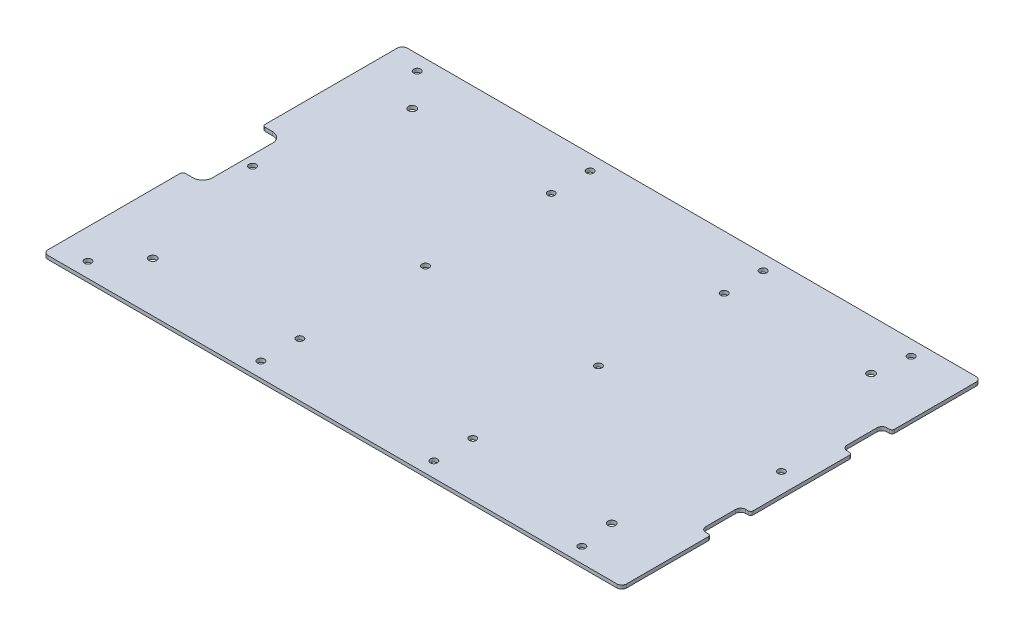
SolidWorks part; units mm, degrees
material "1060 Alloy"
ref_plane "Front" through (0, 0, 0) normal (0, 0, 1) x (1, 0, 0)
ref_plane "Top" through (0, 0, 0) normal (0, 1, 0) x (1, 0, 0)
ref_plane "Right" through (0, 0, 0) normal (1, 0, 0) x (0, 0, -1)
sketch "Sketch1" plane through (0, 0, 0) normal (0, 1, 0) x (1, 0, 0)
  line L0 (-55.0333, 0) -> (-165.1, 0) construction
  line L1 (-180.975, 114.3) -> (180.975, 114.3)
  line L2 (-184.15, 111.125) -> (-184.15, -111.125)
  line L3 (-180.975, -114.3) -> (180.975, -114.3)
  line L4 (184.15, 111.125) -> (184.15, -111.125)
  line L5 (-184.15, 114.3) -> (184.15, -114.3) construction
  line L6 (-184.15, -114.3) -> (184.15, 114.3) construction
  line L7 (-165.1, -104.775) -> (165.1, -104.775) construction
  line L8 (-165.1, -104.775) -> (-165.1, 104.775) construction
  line L9 (-165.1, 104.775) -> (165.1, 104.775) construction
  line L10 (165.1, -104.775) -> (165.1, 104.775) construction
  line L11 (-165.1, -104.775) -> (165.1, 104.775) construction
  line L12 (-165.1, 104.775) -> (165.1, -104.775) construction
  line L13 (-55.0333, -104.775) -> (55.0333, -104.775) construction
  line L14 (-55.0333, -104.775) -> (-55.0333, 104.775) construction
  line L15 (-55.0333, 104.775) -> (55.0333, 104.775) construction
  line L16 (55.0333, -104.775) -> (55.0333, 104.775) construction
  line L17 (-55.0333, -104.775) -> (55.0333, 104.775) construction
  line L18 (-55.0333, 104.775) -> (55.0333, -104.775) construction
  line L19 (55.0333, 0) -> (165.1, 0) construction
  line L20 (-55.0333, 0) -> (55.0333, 0) construction
  line L31 (-55.0291, 80.01) -> (55.0291, 80.01) construction
  line L32 (149.225, -104.775) -> (149.225, 104.775) construction
  line L33 (-55.0291, 80.01) -> (-55.0291, -80.01) construction
  line L34 (-55.0291, -80.01) -> (55.0291, -80.01) construction
  line L35 (55.0291, 80.01) -> (55.0291, -80.01) construction
  line L36 (-55.0291, 80.01) -> (55.0291, -80.01) construction
  line L37 (-55.0291, -80.01) -> (55.0291, 80.01) construction
  circle A0 centre (-165.1, 104.775) radius 2.2479
  circle A1 centre (-55.0333, 104.775) radius 2.2479
  circle A2 centre (55.0333, 104.775) radius 2.2479
  circle A3 centre (165.1, 104.775) radius 2.2479 construction
  circle A4 centre (165.1, -104.775) radius 2.2479 construction
  circle A5 centre (55.0333, -104.775) radius 2.2479
  circle A6 centre (-55.0333, -104.775) radius 2.2479
  circle A7 centre (-165.1, -104.775) radius 2.2479
  circle A12 centre (-55.0333, 0) radius 2.2479
  circle A13 centre (55.0333, 0) radius 2.2479
  arc A14 (184.15, 111.125) -> (180.975, 114.3) centre (180.975, 111.125) ccw
  arc A15 (184.15, -111.125) -> (180.975, -114.3) centre (180.975, -111.125) cw
  arc A16 (-180.975, -114.3) -> (-184.15, -111.125) centre (-180.975, -111.125) cw
  arc A17 (-180.975, 114.3) -> (-184.15, 111.125) centre (-180.975, 111.125) ccw
  circle A24 centre (149.225, -104.775) radius 2.2479
  circle A25 centre (149.225, 104.775) radius 2.2479
  circle A26 centre (55.0291, -80.01) radius 2.2479
  circle A27 centre (-55.0291, -80.01) radius 2.2479
  circle A28 centre (-55.0291, 80.01) radius 2.2479
  circle A29 centre (55.0291, 80.01) radius 2.2479
  circle A30 centre (171.45, 0) radius 2.2479
  circle A31 centre (-165.1, 0) radius 2.2479
  circle A32 centre (-146.05, 82.55) radius 2.4574 construction
  circle A33 centre (-146.05, 82.55) radius 2.4575
  circle A34 centre (146.05, 82.55) radius 2.4574 construction
  circle A35 centre (146.05, 82.55) radius 2.4575
  circle A36 centre (-146.05, -82.55) radius 2.4574 construction
  circle A37 centre (-146.05, -82.55) radius 2.4575
  circle A38 centre (146.05, -82.55) radius 2.4574 construction
  circle A39 centre (146.05, -82.55) radius 2.4575
  point P0 (0, 0)
  point P6 (0, 0)
  point P11 (0, 0)
  point P28 (0, 0)
  point P29 (0, 0)
  point P32 (0, 0)
  dimension "D5" = 4.4958
  dimension "D8" = 4.4958
  dimension "D11" = 3.175
  dimension "D10" = 12.7
  dimension "D12" = 19.05
  dimension "D13" = 110.0667
  dimension "D1" = 368.3
  dimension "D2" = 228.6
  dimension "D3" = 9.525
  dimension "D4" = 19.05
  dimension "D6" = 160.02
  dimension "D7" = 34.925
  dimension "D9" = 110.0582
extrude "Boss-Extrude1" add sketch "Sketch1" along normal blind 2.286
sketch "Sketch2" plane through (0, 0, 0) normal (0, -1, 0) x (1, 0, 0)
  line L5 (184.15, 111.125) -> (184.15, -111.125) construction
  line L6 (184.15, 57.658) -> (180.975, 57.658)
  line L7 (184.15, 57.658) -> (184.15, 32.258)
  line L8 (184.15, 32.258) -> (180.975, 32.258)
  line L9 (177.8, 54.483) -> (177.8, 35.433)
  line L10 (-184.15, 0) -> (185.7248, 0) construction
  line L11 (-184.15, -111.125) -> (-184.15, 111.125) construction
  line L12 (185.7248, -116.6368) -> (185.7248, 116.6368) construction
  line L13 (177.8, 44.958) -> (184.15, 44.958) construction
  line L14 (184.15, -32.258) -> (180.975, -32.258)
  line L15 (184.15, -57.658) -> (184.15, -32.258)
  line L16 (177.8, -54.483) -> (177.8, -35.433)
  line L17 (184.15, -57.658) -> (180.975, -57.658)
  line L19 (-184.15, 25.4) -> (-177.8, 25.4)
  line L20 (-184.15, 25.4) -> (-184.15, -25.4)
  line L21 (-184.15, -25.4) -> (-177.8, -25.4)
  line L22 (-171.45, 19.05) -> (-171.45, -19.05)
  arc A0 (180.975, -57.658) -> (177.8, -54.483) centre (180.975, -54.483) cw
  arc A1 (177.8, -35.433) -> (180.975, -32.258) centre (180.975, -35.433) cw
  arc A2 (177.8, 35.433) -> (180.975, 32.258) centre (180.975, 35.433) ccw
  arc A3 (177.8, 54.483) -> (180.975, 57.658) centre (180.975, 54.483) cw
  arc A4 (-171.45, -19.05) -> (-177.8, -25.4) centre (-177.8, -19.05) cw
  arc A5 (-171.45, 19.05) -> (-177.8, 25.4) centre (-177.8, 19.05) ccw
  point P20 (177.8, -57.658)
  point P23 (177.8, -32.258)
  point P26 (177.8, 32.258)
  point P29 (177.8, 57.658)
  point P38 (-171.45, 25.4)
  dimension "D4" = 3.175
  dimension "D7" = 6.35
  dimension "D1" = 25.4
  dimension "D2" = 44.958
  dimension "D3" = 6.35
  dimension "D5" = 50.8
  dimension "D6" = 12.7
extrude "Cut-Extrude1" cut sketch "Sketch2" against normal through all
fillet "Fillet1" radius 1.5875 6 edges at (184.15, 1.143, -57.658) (184.15, 1.143, -32.258) (184.15, 1.143, 32.258) (184.15, 1.143, 57.658) (-184.15, 1.143, -25.4) (-184.15, 1.143, 25.4)
sketch "Sketch3" plane through (0, 2.286, 0) normal (0, 1, 0) x (1, 0, 0)
  line L0 (-198.0256, -111.0509) -> (-198.0256, 117.5491)
  line L1 (204.2781, -126.2696) -> (-1014.9219, -126.2696)
  line L2 (204.2781, -126.2696) -> (204.2781, 1092.9304)
  line L3 (204.2781, 1092.9304) -> (-1014.9219, 1092.9304)
  line L4 (-1014.9219, -126.2696) -> (-1014.9219, 1092.9304)
  line L5 (182.9744, -111.0509) -> (-185.3256, -111.0509)
  line L6 (182.9744, -111.0509) -> (182.9744, 117.5491)
  line L7 (182.9744, 117.5491) -> (-185.3256, 117.5491)
  line L8 (-185.3256, -111.0509) -> (-185.3256, 117.5491)
  line L9 (-198.0256, -111.0509) -> (-566.3256, -111.0509)
  line L10 (-566.3256, -111.0509) -> (-566.3256, 117.5491)
  line L11 (-198.0256, 117.5491) -> (-566.3256, 117.5491)
  line L12 (-579.0256, -111.0509) -> (-579.0256, 117.5491)
  line L13 (-579.0256, -111.0509) -> (-947.3256, -111.0509)
  line L14 (-947.3256, -111.0509) -> (-947.3256, 117.5491)
  line L15 (-579.0256, 117.5491) -> (-947.3256, 117.5491)
  line L16 (-198.0256, 130.2491) -> (-198.0256, 358.8491)
  line L17 (-198.0256, 130.2491) -> (-566.3256, 130.2491)
  line L18 (-566.3256, 130.2491) -> (-566.3256, 358.8491)
  line L19 (-198.0256, 358.8491) -> (-566.3256, 358.8491)
  line L20 (-579.0256, 130.2491) -> (-579.0256, 358.8491)
  line L21 (-579.0256, 130.2491) -> (-947.3256, 130.2491)
  line L22 (-947.3256, 130.2491) -> (-947.3256, 358.8491)
  line L23 (-579.0256, 358.8491) -> (-947.3256, 358.8491)
  line L24 (-198.0256, 371.5491) -> (-198.0256, 600.1491)
  line L25 (-198.0256, 371.5491) -> (-566.3256, 371.5491)
  line L26 (-566.3256, 371.5491) -> (-566.3256, 600.1491)
  line L27 (-198.0256, 600.1491) -> (-566.3256, 600.1491)
  line L28 (-579.0256, 371.5491) -> (-579.0256, 600.1491)
  line L29 (-579.0256, 371.5491) -> (-947.3256, 371.5491)
  line L30 (-947.3256, 371.5491) -> (-947.3256, 600.1491)
  line L31 (-579.0256, 600.1491) -> (-947.3256, 600.1491)
  line L32 (-198.0256, 612.8491) -> (-198.0256, 841.4491)
  line L33 (-198.0256, 612.8491) -> (-566.3256, 612.8491)
  line L34 (-566.3256, 612.8491) -> (-566.3256, 841.4491)
  line L35 (-198.0256, 841.4491) -> (-566.3256, 841.4491)
  line L36 (-579.0256, 612.8491) -> (-579.0256, 841.4491)
  line L37 (-579.0256, 612.8491) -> (-947.3256, 612.8491)
  line L38 (-947.3256, 612.8491) -> (-947.3256, 841.4491)
  line L39 (-579.0256, 841.4491) -> (-947.3256, 841.4491)
  line L40 (-198.0256, 854.1491) -> (-198.0256, 1082.7491)
  line L41 (-198.0256, 854.1491) -> (-566.3256, 854.1491)
  line L42 (-566.3256, 854.1491) -> (-566.3256, 1082.7491)
  line L43 (-198.0256, 1082.7491) -> (-566.3256, 1082.7491)
  line L44 (-579.0256, 854.1491) -> (-579.0256, 1082.7491)
  line L45 (-579.0256, 854.1491) -> (-947.3256, 854.1491)
  line L46 (-947.3256, 854.1491) -> (-947.3256, 1082.7491)
  line L47 (-579.0256, 1082.7491) -> (-947.3256, 1082.7491)
  line L48 (182.9744, 130.2491) -> (182.9744, 358.8491)
  line L49 (182.9744, 130.2491) -> (-185.3256, 130.2491)
  line L50 (-185.3256, 130.2491) -> (-185.3256, 358.8491)
  line L51 (182.9744, 358.8491) -> (-185.3256, 358.8491)
  line L52 (182.9744, 371.5491) -> (182.9744, 600.1491)
  line L53 (182.9744, 371.5491) -> (-185.3256, 371.5491)
  line L54 (-185.3256, 371.5491) -> (-185.3256, 600.1491)
  line L55 (182.9744, 600.1491) -> (-185.3256, 600.1491)
  line L56 (182.9744, 612.8491) -> (182.9744, 841.4491)
  line L57 (182.9744, 612.8491) -> (-185.3256, 612.8491)
  line L58 (-185.3256, 612.8491) -> (-185.3256, 841.4491)
  line L59 (182.9744, 841.4491) -> (-185.3256, 841.4491)
  line L60 (182.9744, 854.1491) -> (182.9744, 1082.7491)
  line L61 (182.9744, 854.1491) -> (-185.3256, 854.1491)
  line L62 (-185.3256, 854.1491) -> (-185.3256, 1082.7491)
  line L63 (182.9744, 1082.7491) -> (-185.3256, 1082.7491)
  dimension "D1" = 1219.2
  dimension "D2" = 1219.2
  dimension "D3" = 368.3
  dimension "D4" = 228.6
  dimension "D5" = 3
  dimension "D6" = 5
